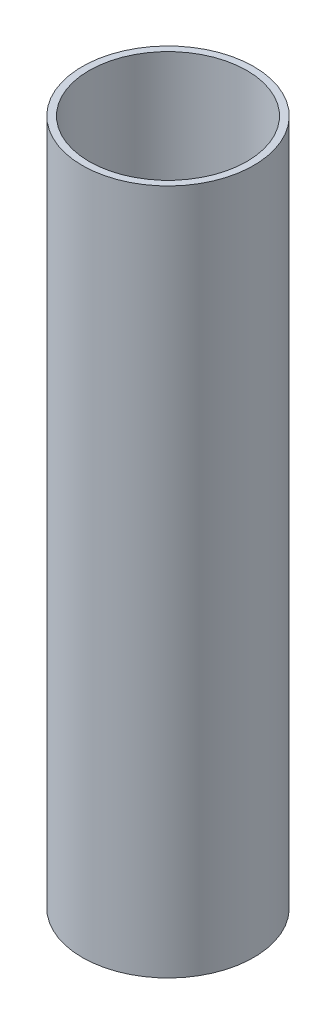
SolidWorks part; units mm, degrees
material "3.1355 (EN-AW 2024)"
ref_plane "Front" through (0, 0, 0) normal (0, 0, 1) x (1, 0, 0)
ref_plane "Top" through (0, 0, 0) normal (0, 1, 0) x (1, 0, 0)
ref_plane "Right" through (0, 0, 0) normal (1, 0, 0) x (0, 0, -1)
sketch "Эскиз1" plane through (0, 0, 0) normal (0, 1, 0) x (1, 0, 0)
  circle A0 centre (0, 0) radius 12.5
  circle A1 centre (0, 0) radius 11.5
  dimension "D1" = 25
  dimension "D2" = 23
extrude "Бобышка-Вытянуть1" add sketch "Эскиз1" along normal blind 100
